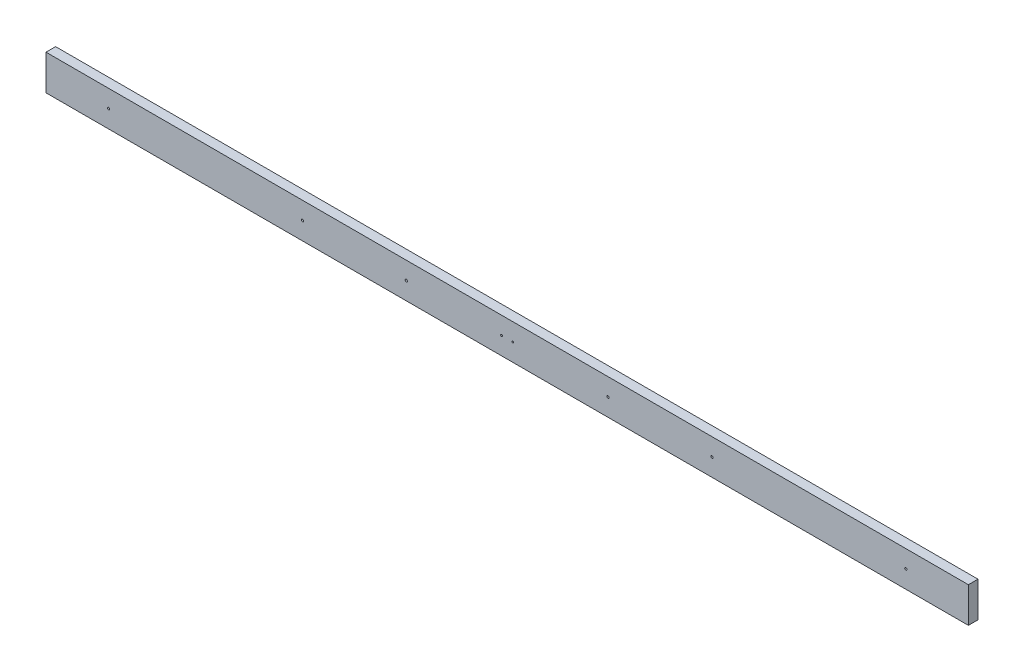
SolidWorks part; units mm, degrees
ref_plane "Front Plane" through (0, 0, 0) normal (0, 0, 1) x (1, 0, 0)
ref_plane "Top Plane" through (0, 0, 0) normal (0, 1, 0) x (1, 0, 0)
ref_plane "Right Plane" through (0, 0, 0) normal (1, 0, 0) x (0, 0, -1)
sketch "Sketch1" plane through (0, 0, 0) normal (0, 0, 1) x (1, 0, 0)
  line L1 (-1828.8, -69.85) -> (1828.8, -69.85)
  line L2 (-1828.8, -69.85) -> (-1828.8, 69.85)
  line L3 (-1828.8, 69.85) -> (1828.8, 69.85)
  line L4 (1828.8, -69.85) -> (1828.8, 69.85)
  line L5 (-1828.8, -69.85) -> (1828.8, 69.85) construction
  line L6 (-1828.8, 69.85) -> (1828.8, -69.85) construction
  point P0 (0, 0)
  dimension "D1" = 3657.6
  dimension "D2" = 139.7
extrude "Boss-Extrude1" add sketch "Sketch1" along normal blind 38.1
sketch "Sketch3" plane through (0, 0, 38.1) normal (0, 0, 1) x (1, 0, 0)
  line L0 (0, -69.85) -> (0, 69.85) construction
  line L1 (-1828.8, -69.85) -> (1828.8, -69.85) construction
  line L2 (1828.8, 69.85) -> (-1828.8, 69.85) construction
  line L3 (-28.575, -7.9375) -> (28.575, -7.9375) construction
  line L4 (-28.575, -7.9375) -> (-28.575, 7.9375) construction
  line L5 (-28.575, 7.9375) -> (28.575, 7.9375) construction
  line L6 (28.575, -7.9375) -> (28.575, 7.9375) construction
  line L7 (-22.225, 0) -> (22.225, 0) construction
  circle A0 centre (-22.225, 0) radius 3.5719
  circle A1 centre (22.225, 0) radius 3.5719
  point P14 (-28.575, 0)
  dimension "D8" = 7.1437
  dimension "D9" = 7.1437
  dimension "D1" = 15.875
  dimension "D2" = 7.9375
  dimension "D3" = 44.45
  dimension "D4" = 6.35
  dimension "D5" = 57.15
  dimension "D10" = 7.9375
extrude "Cut-Extrude2" cut sketch "Sketch3" against normal through all contours A0 | A1
sketch "Sketch4" plane through (0, 0, 38.1) normal (0, 0, 1) x (1, 0, 0)
  line L0 (0, 589.6071) -> (0, -768.8477)
  line L1 (762, 589.6071) -> (762, -768.8477)
  dimension "D1" = 762
sketch "Sketch5" plane through (0, 0, 38.1) normal (0, 0, 1) x (1, 0, 0)
  line L0 (-400, 0) -> (400, 0) construction
  circle A0 centre (400, 0) radius 4.4996
  circle A1 centre (-400, 0) radius 4.4996
  point P4 (0, 0)
  dimension "D2" = 8.9992
  dimension "D3" = 8.9992
  dimension "D1" = 800
extrude "Cut-Extrude3" cut sketch "Sketch5" against normal through all
sketch "Sketch6" plane through (0, 0, 38.1) normal (0, 0, 1) x (1, 0, 0)
  line L0 (1828.8, 0) -> (-1828.8, 0) construction
  line L1 (1828.8, -69.85) -> (1828.8, 69.85) construction
  line L2 (-1828.8, 69.85) -> (-1828.8, -69.85) construction
  line L3 (0, 69.85) -> (0, -69.85) construction
  line L4 (1828.8, 69.85) -> (-1828.8, 69.85) construction
  line L6 (-789.94, -403.86) -> (789.94, -403.86) construction
  line L7 (-789.94, -403.86) -> (-789.94, 403.86) construction
  line L8 (-789.94, 403.86) -> (789.94, 403.86) construction
  line L9 (789.94, -403.86) -> (789.94, 403.86) construction
  line L10 (-789.94, -403.86) -> (789.94, 403.86) construction
  line L11 (-789.94, 403.86) -> (789.94, -403.86) construction
  circle A0 centre (811.94, 0) radius 4.4996
  circle A1 centre (1580.6608, 0) radius 4.4996
  circle A3 centre (-1580.6608, 0) radius 4.4996
  circle A4 centre (-811.94, 0) radius 4.4996
  point P15 (400, 0)
  point P21 (0, 0)
  point P27 (806.965, 0)
  point P28 (835.1092, 0)
  dimension "D2" = 8.9992
  dimension "D3" = 8.9992
  dimension "D1" = 768.7208
  dimension "D4" = 1579.88
  dimension "D5" = 807.72
  dimension "D6" = 22
extrude "Cut-Extrude4" cut sketch "Sketch6" against normal through all
sketch "Sketch7" plane through (0, 0, 38.1) normal (0, 0, 1) x (1, 0, 0)
  point P0 (-811.94, 0)
  point P1 (-1580.6608, 0)
  point P3 (400, 0)
  point P5 (811.94, 0)
  point P7 (1580.6608, 0)
